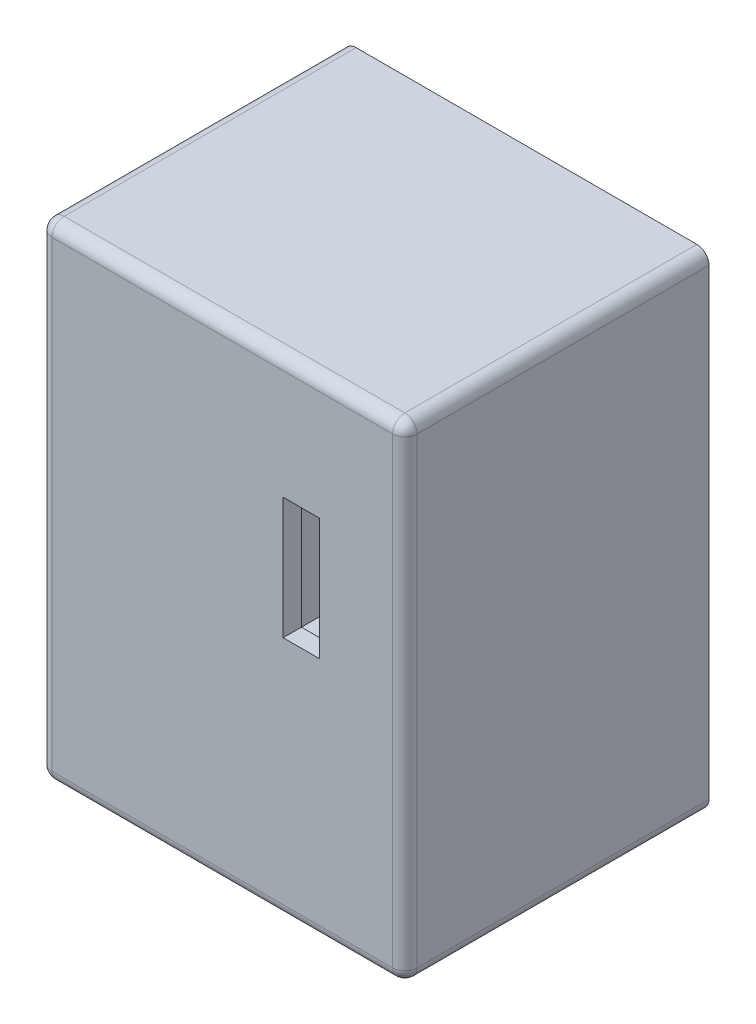
SolidWorks part; units mm, degrees
ref_plane "Front Plane" through (0, 0, 0) normal (0, 0, 1) x (1, 0, 0)
ref_plane "Top Plane" through (0, 0, 0) normal (0, 1, 0) x (1, 0, 0)
ref_plane "Right Plane" through (0, 0, 0) normal (1, 0, 0) x (0, 0, -1)
sketch "Sketch2" plane through (0, 0, 0) normal (0, 0, 1) x (1, 0, 0)
  line L1 (0, 0) -> (30, 0)
  line L2 (0, 0) -> (0, 40)
  line L3 (0, 40) -> (30, 40)
  line L4 (30, 0) -> (30, 40)
  dimension "D1" = 30
  dimension "D2" = 40
extrude "Boss-Extrude2" add sketch "Sketch2" along normal blind 25 contours L3 L4 L1 L2
fillet "Fillet2" radius 1 4 edges at (15, 0, 25) (30, 20, 25) (0, 20, 25) (15, 40, 25)
fillet "Fillet3" radius 1 8 edges at (29.7071, 0.2929, 24.7071) (0.2929, 0.2929, 24.7071) (0.2929, 39.7071, 24.7071) (29.7071, 39.7071, 24.7071) (30, 0, 12) (0, 0, 12) (0, 40, 12) (30, 40, 12)
shell "Shell1" thickness 1.5 removed face at (15, 20, 0)
fillet "Fillet4" radius 1 4 edges at (15, 38.5, 23.5) (15, 1.5, 23.5) (28.5, 20, 23.5) (1.5, 20, 23.5)
sketch "Sketch5" plane through (0, 0, 25) normal (0, 0, 1) x (1, 0, 0)
  line L1 (20, 30) -> (23, 30)
  line L2 (20, 30) -> (20, 20)
  line L3 (20, 20) -> (23, 20)
  line L4 (23, 30) -> (23, 20)
  line L6 (1, 40) -> (29, 40) construction
  dimension "D1" = 10
  dimension "D2" = 20
extrude "Cut-Extrude1" cut sketch "Sketch5" against normal through all
